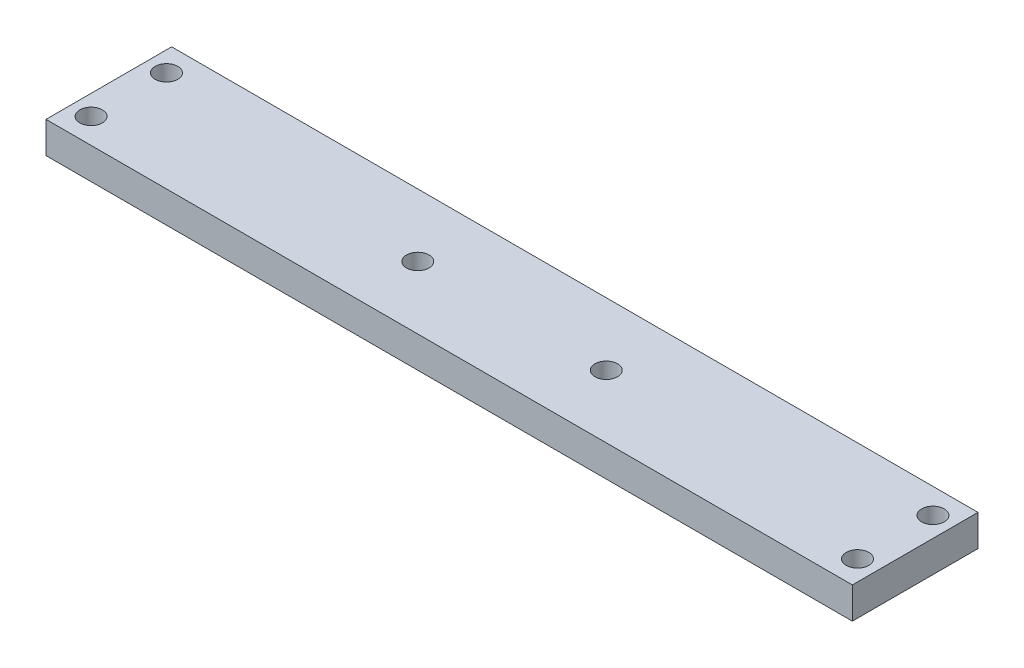
SolidWorks part; units mm, degrees
ref_plane "Front Plane" through (0, 0, 0) normal (0, 0, 1) x (1, 0, 0)
ref_plane "Top Plane" through (0, 0, 0) normal (0, 1, 0) x (1, 0, 0)
ref_plane "Right Plane" through (0, 0, 0) normal (1, 0, 0) x (0, 0, -1)
sketch "Sketch2" plane through (0, 0, 0) normal (0, 1, 0) x (1, 0, 0)
  line L1 (-39.8374, 20.9756) -> (88.5126, 20.9756)
  line L2 (-39.8374, 20.9756) -> (-39.8374, 0.9756)
  line L3 (-39.8374, 0.9756) -> (88.5126, 0.9756)
  line L4 (88.5126, 20.9756) -> (88.5126, 0.9756)
  dimension "D1" = 20
  dimension "D2" = 128.35
extrude "Boss-Extrude1" add sketch "Sketch2" along normal blind 5
sketch "Sketch3" plane through (0, 5, 0) normal (0, 1, 0) x (1, 0, 0)
  line L2 (-39.8374, 20.9756) -> (-39.8374, 0.9756) construction
  line L3 (88.5126, 0.9756) -> (88.5126, 20.9756) construction
  line L4 (-36.6624, 16.9756) -> (-36.6624, 4.9756) construction
  line L6 (-39.8374, 10.9756) -> (-36.6624, 10.9756) construction
  point P0 (-36.6624, 16.9756)
  point P1 (-36.6624, 4.9756)
  point P9 (85.3376, 16.9756)
  point P11 (85.3376, 4.9756)
  dimension "D1" = 12
  dimension "D3" = 3.175
  dimension "D4" = 3.175
  dimension "D5" = 3.175
  dimension "D6" = 122
hole_wizard "M3 Clearance Hole1" positions "Sketch3" profile "Sketch4" hole size "M3" standard "ANSI Metric" end condition through all
sketch "Sketch4" plane through (-36.6624, 5, -16.9756) normal (1, 0, 0) x (0, 0, 1)
  line L0 (0, 0) -> (0, 5)
  line L1 (0, 5) -> (1.8, 5)
  line L2 (1.8, 5) -> (1.8, 0)
  line L5 (1.8, 0) -> (0, 0)
  line L11 (0, -6.35) -> (0, 107.95) construction
  dimension "Thru Hole Dia." = 3.6
  dimension "Thru Hole Depth" = 5
sketch "Sketch5" plane through (0, 5, 0) normal (0, 1, 0) x (1, 0, 0)
  line L2 (9.3376, 10.9756) -> (39.3376, 10.9756) construction
  line L3 (88.5126, 20.9756) -> (-39.8374, 20.9756) construction
  line L4 (24.3376, 20.9756) -> (24.3376, 0.9756) construction
  line L5 (-39.8374, 0.9756) -> (88.5126, 0.9756) construction
  point P0 (9.3376, 10.9756)
  point P1 (39.3376, 10.9756)
  point P10 (24.3376, 20.9756)
  point P11 (24.3376, 10.9756)
  dimension "D1" = 30
hole_wizard "M3 Clearance Hole2" positions "Sketch5" profile "Sketch6" hole size "M3" standard "ANSI Metric" end condition through all
sketch "Sketch6" plane through (9.3376, 5, -10.9756) normal (1, 0, 0) x (0, 0, 1)
  line L0 (0, 0) -> (0, 5)
  line L1 (0, 5) -> (1.8, 5)
  line L2 (1.8, 5) -> (1.8, 0)
  line L5 (1.8, 0) -> (0, 0)
  line L11 (0, -6.35) -> (0, 107.95) construction
  dimension "Thru Hole Dia." = 3.6
  dimension "Thru Hole Depth" = 5
